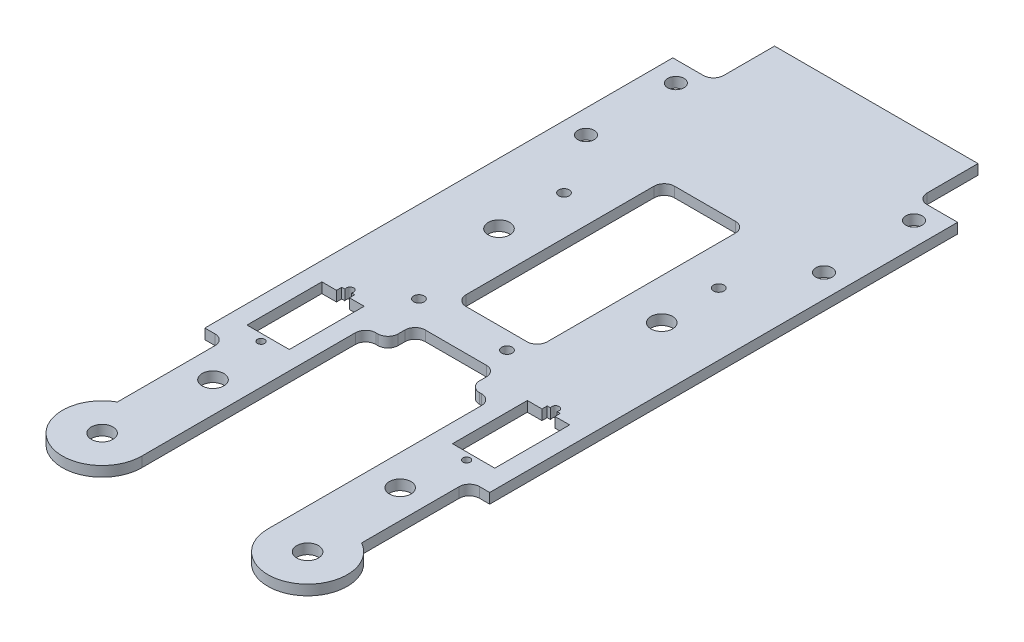
SolidWorks part; units mm, degrees
material "6061-T4 (SS)"
ref_plane "Front Plane" through (0, 0, 0) normal (0, 0, 1) x (1, 0, 0)
ref_plane "Top Plane" through (0, 0, 0) normal (0, 1, 0) x (1, 0, 0)
ref_plane "Right Plane" through (0, 0, 0) normal (1, 0, 0) x (0, 0, -1)
sketch "Sketch1" plane through (0, 0, 0) normal (0, 1, 0) x (1, 0, 0)
  line L1 (-44.45, -114.3) -> (44.45, -114.3)
  line L2 (-44.45, -114.3) -> (-44.45, 114.3)
  line L3 (-44.45, 114.3) -> (44.45, 114.3)
  line L4 (44.45, -114.3) -> (44.45, 114.3)
  line L5 (-44.45, -114.3) -> (44.45, 114.3) construction
  line L6 (-44.45, 114.3) -> (44.45, -114.3) construction
  point P0 (0, 0)
  dimension "D1" = 88.9
  dimension "D2" = 228.6
extrude "Boss-Extrude1" add sketch "Sketch1" along normal blind 3.175
sketch "Sketch11" plane through (0, 3.175, 0) normal (0, 1, 0) x (1, 0, 0)
  line L0 (0, 31.75) -> (97.4414, 31.75) construction
  line L10 (0, 0) -> (0, 114.3) construction
  line L14 (44.45, 114.3) -> (-44.45, 114.3) construction
  line L15 (0, 0) -> (117.475, 0) construction
  circle A0 centre (-26.289, 4.9828) radius 1.25
  circle A1 centre (-25.019, 53.1832) radius 1.25
  circle A2 centre (25.781, 38.1972) radius 1.25
  circle A3 centre (25.781, 10.0628) radius 1.25
  dimension "D3" = 2.5
  dimension "D5" = 2.5
  dimension "D7" = 31.75
  dimension "D9" = 25.781
  dimension "D4" = 2.5
  dimension "D6" = 2.5
  dimension "D2" = 25.019
  dimension "D8" = 26.289
  dimension "D10" = 6.4472
  dimension "D11" = 25.781
  dimension "D12" = 21.6872
  dimension "D13" = 26.7672
  dimension "D14" = 21.4332
extrude "Cut-Extrude12" [suppressed] cut sketch "Sketch11" against normal through all
sketch "Sketch18" plane through (0, 3.175, 0) normal (0, 1, 0) x (1, 0, 0)
  line L0 (44.45, 79.883) -> (-44.45, 79.883) construction
  line L1 (44.45, -114.3) -> (44.45, 114.3) construction
  line L2 (-44.45, 114.3) -> (-44.45, -114.3) construction
  line L3 (44.45, 114.3) -> (-44.45, 114.3) construction
  line L4 (0, 79.883) -> (0, -114.3) construction
  line L5 (-44.45, -114.3) -> (44.45, -114.3) construction
  line L6 (19.05, 79.883) -> (19.05, 6.35) construction
  line L7 (-19.05, 79.883) -> (-19.05, 6.35) construction
  line L8 (19.05, 6.35) -> (-19.05, 6.35) construction
  circle A0 centre (-24.9365, 60.833) radius 1.6319
  circle A1 centre (24.9365, 59.2455) radius 1.6319
  circle A2 centre (-18.9039, 9.525) radius 1.632
  circle A3 centre (8.6805, 9.398) radius 1.632
  dimension "D4" = 3.2639
  dimension "D9" = 3.2639
  dimension "D11" = 3.2639
  dimension "D13" = 3.2639
  dimension "D1" = 34.417
  dimension "D2" = 19.05
  dimension "D3" = 73.533
  dimension "D5" = 24.9365
  dimension "D6" = 19.05
  dimension "D7" = 24.9365
  dimension "D8" = 1.5875
  dimension "D10" = 6.0325
  dimension "D12" = 51.308
  dimension "D14" = 0.127
  dimension "D15" = 27.5844
sketch "Sketch12" plane through (0, 3.175, 0) normal (0, 1, 0) x (1, 0, 0)
  line L0 (0, 0) -> (44.45, 0) construction
  line L1 (44.45, -114.3) -> (44.45, 114.3) construction
  line L2 (0, 0) -> (0, 114.3) construction
  line L3 (44.45, 114.3) -> (-44.45, 114.3) construction
  line L4 (44.45, -44.45) -> (-44.45, -44.45) construction
  line L5 (-19.685, -69.85) -> (19.685, -69.85)
  line L6 (-19.685, -69.85) -> (-19.685, -6.35)
  line L7 (-19.685, -6.35) -> (19.685, -6.35)
  line L8 (19.685, -69.85) -> (19.685, -6.35)
  line L9 (-19.685, -69.85) -> (19.685, -6.35) construction
  line L10 (-19.685, -6.35) -> (19.685, -69.85) construction
  line L11 (-44.45, 114.3) -> (-44.45, -114.3) construction
  line L12 (0, -38.1) -> (0, -114.3) construction
  line L13 (-44.45, -114.3) -> (44.45, -114.3) construction
  circle A0 centre (29.21, -44.45) radius 3.3782
  circle A1 centre (-29.21, -44.45) radius 3.3782
  point P5 (0, -38.1)
  dimension "D5" = 6.7564
  dimension "D1" = 63.5
  dimension "D2" = 38.1
  dimension "D3" = 39.37
  dimension "D4" = 25.4
  dimension "D6" = 58.42
extrude "Cut-Extrude13" cut sketch "Sketch12" against normal through all
sketch "Sketch14" plane through (0, 0, 0) normal (0, -1, 0) x (-1, 0, 0)
  line L0 (0, 114.3) -> (0, 31.056) construction
  line L1 (-44.45, 114.3) -> (44.45, 114.3) construction
  line L2 (0, 114.3) -> (-44.45, 114.3) construction
  line L3 (-41.91, 114.3) -> (-41.91, 67.4804) construction
  line L5 (-32.385, 114.3) -> (-32.385, 67.4804) construction
  line L6 (-32.385, 107.95) -> (-41.91, 107.95) construction
  line L7 (-32.385, 93.9165) -> (-41.91, 93.9165) construction
  line L8 (-44.45, -114.3) -> (-44.45, 114.3) construction
  circle A0 centre (-37.1475, 107.95) radius 2.5527
  circle A1 centre (-37.1475, 79.883) radius 2.5527
  circle A2 centre (37.1475, 107.95) radius 2.5527
  circle A3 centre (37.1475, 79.883) radius 2.5527
  point P25 (0, 0)
  point P27 (0, 0)
  point P28 (-41.1256, 114.3)
  point P29 (0, 0)
  dimension "D4" = 5.1054
  dimension "D1" = 2.54
  dimension "D2" = 9.525
  dimension "D3" = 6.35
  dimension "D5" = 14.0335
extrude "Cut-Extrude15" cut sketch "Sketch14" against normal through all
sketch "Sketch15" plane through (0, 0, 0) normal (0, -1, 0) x (1, 0, 0)
  line L0 (44.45, 114.3) -> (44.45, -114.3) construction
  line L1 (-44.45, 114.3) -> (44.45, 114.3)
  line L2 (-44.45, 114.3) -> (-44.45, 57.15)
  line L3 (-44.45, 57.15) -> (44.45, 57.15)
  line L4 (44.45, 114.3) -> (44.45, 57.15)
  line L5 (19.685, 6.35) -> (-19.685, 6.35) construction
  line L6 (0, -36.7665) -> (0, -114.3) construction
  line L7 (12.7, -76.708) -> (12.7, -17.9917)
  line L8 (9.525, -14.8167) -> (-9.525, -14.8167)
  line L9 (44.45, -114.3) -> (-44.45, -114.3) construction
  line L10 (-12.7, -17.9917) -> (-12.7, -76.708)
  line L11 (9.525, -79.883) -> (-9.525, -79.883)
  line L12 (12.7, -76.708) -> (12.7, 6.35) construction
  line L13 (12.7, 6.35) -> (-12.7, 6.35) construction
  line L14 (-12.7, -76.708) -> (-12.7, 6.35) construction
  line L15 (12.7, -79.883) -> (-12.7, 6.35) construction
  line L16 (12.7, 6.35) -> (-12.7, -79.883) construction
  line L17 (12.7, 6.35) -> (-12.7, 6.35)
  line L18 (-12.7, 6.35) -> (-12.7, 1.0583)
  line L19 (-9.525, -2.1167) -> (9.525, -2.1167)
  line L20 (12.7, 1.0583) -> (12.7, 6.35)
  circle A0 centre (-29.21, 44.45) radius 3.3782 construction
  circle A1 centre (-37.1475, -79.883) radius 2.5527 construction
  arc A2 (-9.525, -79.883) -> (-12.7, -76.708) centre (-9.525, -76.708) cw
  arc A3 (9.525, -79.883) -> (12.7, -76.708) centre (9.525, -76.708) ccw
  arc A4 (12.7, -17.9917) -> (9.525, -14.8167) centre (9.525, -17.9917) ccw
  arc A5 (-9.525, -14.8167) -> (-12.7, -17.9917) centre (-9.525, -17.9917) ccw
  arc A6 (-12.7, 1.0583) -> (-9.525, -2.1167) centre (-9.525, 1.0583) ccw
  arc A7 (9.525, -2.1167) -> (12.7, 1.0583) centre (9.525, 1.0583) ccw
  point P35 (12.7, -14.8167)
  point P38 (-12.7, -14.8167)
  point P41 (-12.7, -2.1167)
  point P44 (12.7, -2.1167)
  dimension "D3" = 3.175
  dimension "D7" = 3.175
  dimension "D1" = 12.7
  dimension "D2" = 0
  dimension "D4" = 25.4
  dimension "D5" = 8.4667
  dimension "D6" = 12.7
extrude "Cut-Extrude16" cut sketch "Sketch15" against normal through all
fillet "Fillet1" radius 3.175 4 edges at (19.685, 1.5875, 6.35) (-19.685, 1.5875, 6.35) (-12.7, 1.5875, 6.35) (12.7, 1.5875, 6.35)
extrude "Cut-Extrude18" cut sketch "Sketch18" against normal through all
sketch "Sketch16" plane through (0, 3.175, 0) normal (0, 1, 0) x (1, 0, 0)
  line L0 (44.45, -57.15) -> (44.45, -76.2)
  line L1 (19.685, -57.15) -> (19.685, -76.2)
  line L2 (19.685, -76.2) -> (44.45, -76.2) construction
  line L3 (0, 0) -> (0, -94.827) construction
  line L4 (44.45, -57.15) -> (19.685, -57.15)
  line L5 (-19.685, -57.15) -> (-19.685, -76.2)
  line L6 (-44.45, -57.15) -> (-19.685, -57.15)
  line L7 (-44.45, -57.15) -> (-44.45, -76.2)
  arc A0 (44.45, -76.2) -> (19.685, -76.2) centre (32.0675, -76.2) cw
  arc A1 (-44.45, -76.2) -> (-19.685, -76.2) centre (-32.0675, -76.2) ccw
  circle A2 centre (32.0675, -76.2) radius 3.3782
  circle A3 centre (-32.0675, -76.2) radius 3.3782
  line M12 (-44.45, -57.15) -> (-19.685, -57.15)
  line M16 (19.685, -57.15) -> (44.45, -57.15)
  dimension "D2" = 6.7564
  dimension "D1" = 19.05
extrude "Boss-Extrude2" add sketch "Sketch16" against normal up to surface (3.175 mm away) contours L7 A1 L5 A3 M12 | A0 L0 L1 A2 M16 region at (32.0675, 3.175, 71.4304) region at (-32.0675, 3.175, 71.4304) up to face at (-24.9365, 0, -59.2011)
sketch "Sketch17" plane through (0, 3.175, 0) normal (0, 1, 0) x (1, 0, 0)
  line L0 (38.1, -65.3863) -> (38.1, -34.925)
  line L1 (44.45, -76.2) -> (44.45, 114.3) construction
  line L9 (0, 0) -> (0, -71.3802) construction
  line L15 (41.275, -31.75) -> (44.45, -31.75)
  line L20 (44.45, -31.75) -> (44.45, -76.2)
  line L21 (-41.275, -31.75) -> (-44.45, -31.75)
  line L22 (-38.1, -65.3863) -> (-38.1, -34.925)
  line L23 (-44.45, -31.75) -> (-44.45, -76.2)
  circle A4 centre (32.0675, -76.2) radius 3.3046 construction
  arc A5 (38.1, -34.925) -> (41.275, -31.75) centre (41.275, -34.925) cw
  circle A10 centre (32.0675, -76.2) radius 12.3825 construction
  arc A11 (38.1, -65.3863) -> (44.45, -76.2) centre (32.0675, -76.2) cw
  arc A12 (-38.1, -34.925) -> (-41.275, -31.75) centre (-41.275, -34.925) ccw
  arc A13 (-38.1, -65.3863) -> (-44.45, -76.2) centre (-32.0675, -76.2) ccw
  point P11 (38.1, -31.75)
  dimension "D2" = 3.175
  dimension "D3" = 44.45
  dimension "D1" = 6.35
extrude "Cut-Extrude17" cut sketch "Sketch17" against normal through all
sketch "Sketch19" plane through (0, 3.175, 0) normal (0, 1, 0) x (1, 0, 0)
  line L0 (0, 14.8167) -> (0, 79.883) construction
  line L1 (9.525, 14.8167) -> (-9.525, 14.8167) construction
  line L2 (-9.525, 79.883) -> (9.525, 79.883) construction
  line L3 (-12.7, 47.3498) -> (12.7, 47.3498) construction
  line L4 (-12.7, 17.9917) -> (-12.7, 76.708) construction
  line L5 (12.7, 76.708) -> (12.7, 17.9917) construction
  line L6 (-38.1, 53.975) -> (-12.7, 53.975) construction
  line L7 (-25.4, 53.975) -> (-25.4, 40.9998) construction
  line L9 (-44.45, 114.3) -> (-44.45, -31.75) construction
  circle A0 centre (-25.4, 40.9998) radius 3.3782
  circle A1 centre (25.4, 40.9998) radius 3.3782
  dimension "D1" = 6.7564
  dimension "D2" = 6.35
  dimension "D3" = 6.35
extrude "Cut-Extrude19" cut sketch "Sketch19" against normal through all
sketch "Sketch20" plane through (0, 3.175, 0) normal (0, 1, 0) x (1, 0, 0)
  line L0 (0, 0) -> (0, 61.1006) construction
  line L3 (-25.8445, 3.175) -> (-25.8445, -28.575) construction
  line L6 (-25.4635, -1.016) -> (-38.6715, -1.016) construction
  line L7 (-25.4635, -1.016) -> (-25.4635, -24.384)
  line L8 (-25.4635, -24.384) -> (-38.6715, -24.384)
  line L9 (-38.6715, -1.016) -> (-38.6715, -24.384)
  line L10 (-25.4635, -1.016) -> (-38.6715, -24.384) construction
  line L11 (-25.4635, -24.384) -> (-38.6715, -1.016) construction
  line L13 (-38.2905, 3.175) -> (-38.2905, -28.575) construction
  line L14 (-25.8445, 3.175) -> (-38.2905, -28.575) construction
  line L27 (-32.0675, -76.2) -> (-32.0675, 23.1424) construction
  line L28 (-38.2905, 3.175) -> (-25.8445, -28.575) construction
  line L29 (-38.2905, -28.575) -> (-32.9565, -28.575) construction
  line L30 (-32.9565, -28.575) -> (-32.9565, -27.305) construction
  line L31 (-31.1785, -28.575) -> (-31.1785, -27.305) construction
  line L32 (-25.8445, -28.575) -> (-31.1785, -28.575) construction
  line L33 (-25.8445, 3.175) -> (-31.1785, 3.175) construction
  line L34 (-31.1785, 3.175) -> (-31.1785, 1.905) construction
  line L35 (-32.9565, 3.175) -> (-32.9565, 1.905) construction
  line L36 (-38.2905, 3.175) -> (-32.9565, 3.175) construction
  line L38 (-30.0355, -1.016) -> (-30.0355, 0.6151)
  line L42 (-30.0355, -1.016) -> (-25.4635, -1.016)
  line L44 (-34.0995, -1.016) -> (-34.0995, 0.6151)
  line L45 (-34.0995, -1.016) -> (-38.6715, -1.016)
  line L47 (-33.0574, 0.6151) -> (-34.0995, 0.6151)
  line L48 (-32.0675, 1.1866) -> (-32.0675, 0.0436) construction
  line L49 (-32.0675, 1.1866) -> (-32.0675, 0.0436) construction
  line L50 (-32.0675, 0.6151) -> (-30.8266, 0.6151) construction
  line L51 (-30.0355, 0.6151) -> (-31.0776, 0.6151)
  line L52 (30.0355, -1.016) -> (30.0355, 0.6151)
  line L53 (30.0355, -1.016) -> (25.4635, -1.016)
  line L54 (25.4635, -1.016) -> (25.4635, -24.384)
  line L55 (25.4635, -24.384) -> (38.6715, -24.384)
  line L56 (38.6715, -1.016) -> (38.6715, -24.384)
  line L57 (34.0995, -1.016) -> (38.6715, -1.016)
  line L58 (34.0995, -1.016) -> (34.0995, 0.6151)
  line L59 (33.0574, 0.6151) -> (34.0995, 0.6151)
  line L60 (30.0355, 0.6151) -> (31.0776, 0.6151)
  arc A0 (-32.9565, -27.305) -> (-31.1785, -27.305) centre (-32.0675, -26.5866) cw construction
  arc A1 (-32.9565, 1.905) -> (-31.1785, 1.905) centre (-32.0675, 1.1866) ccw construction
  circle A2 centre (-32.0675, 1.1866) radius 1.143 construction
  circle A3 centre (-32.0675, -26.5866) radius 1.143
  circle A4 centre (32.0675, -26.5866) radius 1.143
  arc A7 (-33.0574, 0.6151) -> (-31.0776, 0.6151) centre (-32.0675, 1.1866) cw
  arc A8 (33.0574, 0.6151) -> (31.0776, 0.6151) centre (32.0675, 1.1866) ccw
  point P10 (-32.0675, -12.7)
  point P16 (-32.0675, -12.7)
  dimension "D1" = 13.208
  dimension "D2" = 23.368
  dimension "D3" = 63.5
  dimension "D4" = 2.032
extrude "Cut-Extrude20" cut sketch "Sketch20" against normal through all
sketch "Sketch21" plane through (0, 0, -114.3) normal (0, 0, -1) x (-1, 0, 0)
  line L1 (44.45, 0) -> (-44.45, 0)
  line L2 (44.45, 0) -> (44.45, 3.175)
  line L3 (44.45, 3.175) -> (-44.45, 3.175)
  line L4 (-44.45, 0) -> (-44.45, 3.175)
extrude "Boss-Extrude3" add sketch "Sketch21" along normal blind 19.05
sketch "Sketch22" plane through (0, 3.175, 0) normal (0, 1, 0) x (1, 0, 0)
  line L0 (0, 79.883) -> (0, 133.35) construction
  line L1 (-44.45, 133.35) -> (-31.75, 133.35)
  line L2 (-44.45, 133.35) -> (-44.45, 114.3)
  line L3 (-44.45, 114.3) -> (-34.925, 114.3)
  line L4 (-31.75, 133.35) -> (-31.75, 117.475)
  line L5 (-9.525, 79.883) -> (9.525, 79.883) construction
  line L6 (44.45, 133.35) -> (-44.45, 133.35) construction
  line L7 (44.45, 114.3) -> (34.925, 114.3)
  line L8 (31.75, 133.35) -> (31.75, 117.475)
  line L9 (44.45, 133.35) -> (31.75, 133.35)
  line L10 (44.45, 133.35) -> (44.45, 114.3)
  arc A0 (-34.925, 114.3) -> (-31.75, 117.475) centre (-34.925, 117.475) ccw
  arc A1 (34.925, 114.3) -> (31.75, 117.475) centre (34.925, 117.475) cw
  point P13 (-31.75, 114.3)
  dimension "D3" = 3.175
  dimension "D1" = 12.7
  dimension "D2" = 19.05
extrude "Cut-Extrude21" cut sketch "Sketch22" against normal through all
